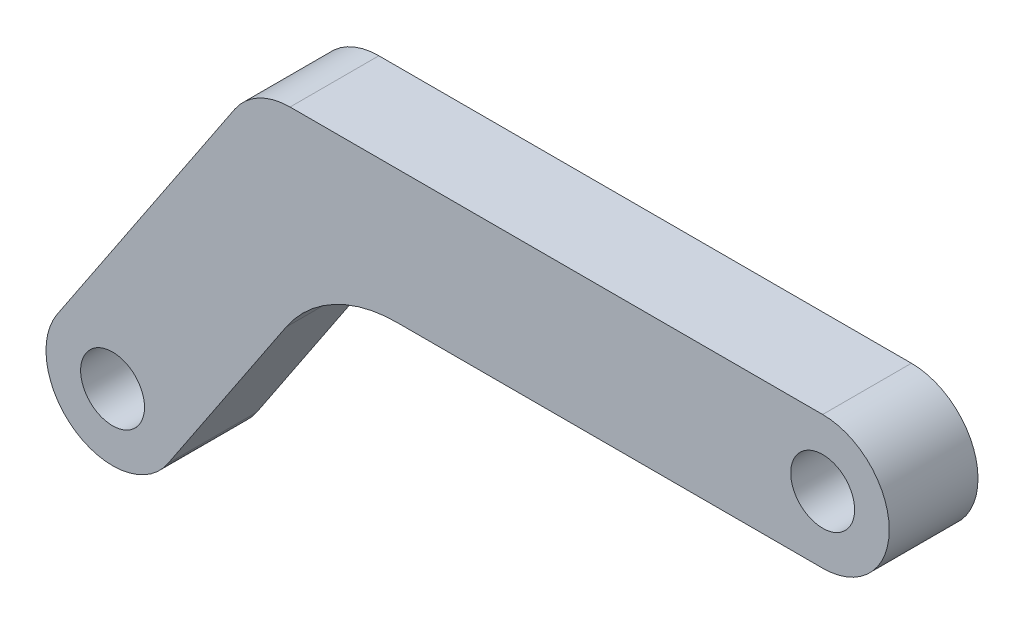
SolidWorks part; units mm, degrees
ref_plane "Front Plane" through (0, 0, 0) normal (0, 0, 1) x (1, 0, 0)
ref_plane "Top Plane" through (0, 0, 0) normal (0, 1, 0) x (1, 0, 0)
ref_plane "Right Plane" through (0, 0, 0) normal (1, 0, 0) x (0, 0, -1)
sketch "Sketch1" plane through (0, 0, 0) normal (0, 0, 1) x (1, 0, 0)
  line L0 (-54.7626, -16.4082) -> (-42.0626, 2.6418)
  line L1 (-38.1, 4.7625) -> (0, 4.7625)
  line L2 (-46.8374, -21.6918) -> (-38.3788, -9.004)
  line L3 (-30.4536, -4.7625) -> (0, -4.7625)
  arc A0 (0, -4.7625) -> (0, 4.7625) centre (0, 0) ccw
  arc A1 (-54.7626, -16.4082) -> (-46.8374, -21.6918) centre (-50.8, -19.05) ccw
  arc A2 (-38.1, 4.7625) -> (-42.0626, 2.6418) centre (-38.1, 0) ccw
  arc A3 (-38.3788, -9.004) -> (-30.4536, -4.7625) centre (-30.4536, -14.2875) cw
  circle A4 centre (0, 0) radius 2.286
  circle A5 centre (-50.8, -19.05) radius 2.286
  dimension "D1" = 9.525
  dimension "D5" = 9.525
  dimension "D6" = 4.572
  dimension "D7" = 4.572
  dimension "D2" = 50.8
  dimension "D3" = 19.05
  dimension "D4" = 38.1
extrude "Boss-Extrude1" add sketch "Sketch1" along normal blind 6.35
